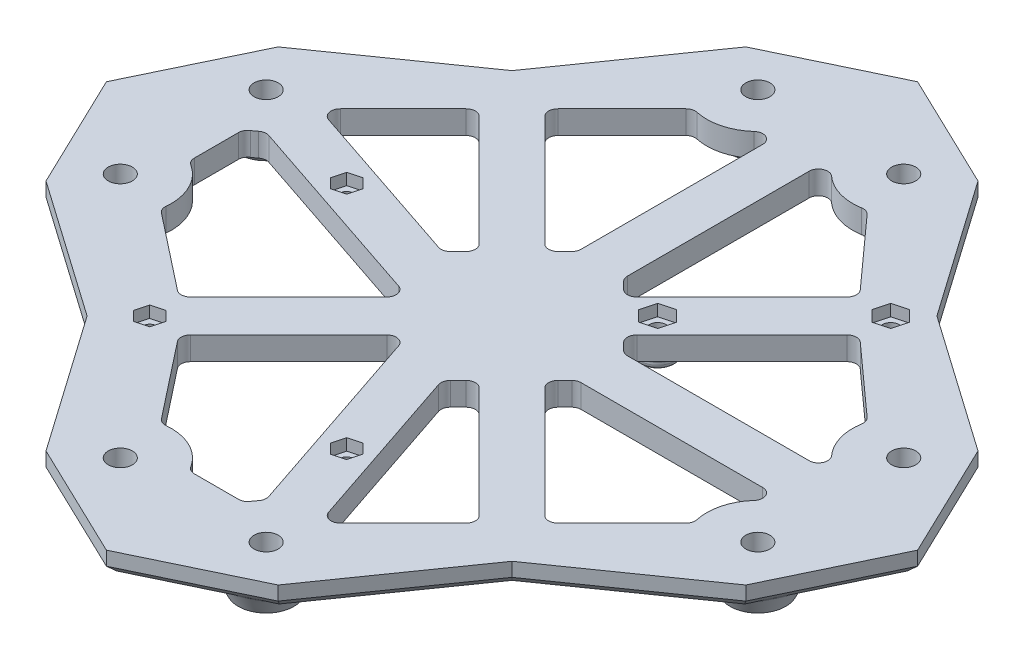
SolidWorks part; units mm, degrees
ref_plane "Front Plane" through (0, 0, 0) normal (0, 0, 1) x (1, 0, 0)
ref_plane "Top Plane" through (0, 0, 0) normal (0, 1, 0) x (1, 0, 0)
ref_plane "Right Plane" through (0, 0, 0) normal (1, 0, 0) x (0, 0, -1)
sketch "Sketch1" plane through (0, 0, 0) normal (0, 1, 0) x (1, 0, 0)
  line L0 (-15.705, 68.65) -> (15.705, 68.65) construction
  line L1 (0, 68.65) -> (0, 0) construction
  line L10 (-15.705, 68.65) -> (0, 87.35) construction
  line L11 (-25.0004, 75.3528) -> (0, 87.35)
  line L12 (0, 87.35) -> (25.0004, 75.3528)
  line L25 (-75.3528, -25.0004) -> (-45.7527, -45.7527)
  line L26 (-25.0004, 75.3528) -> (-15.705, 68.65) construction
  line L27 (0, 87.35) -> (15.705, 68.65) construction
  line L28 (-15.705, 68.65) -> (15.705, 68.65) construction
  line L30 (15.705, 68.65) -> (25.0004, 75.3528) construction
  line L31 (75.3528, 25.0004) -> (87.35, 0)
  line L32 (87.35, 0) -> (75.3528, -25.0004)
  line L33 (68.65, 15.705) -> (68.65, -15.705) construction
  line L34 (68.65, 15.705) -> (87.35, 0) construction
  line L35 (-45.7527, -45.7527) -> (-25.0004, -75.3528)
  line L36 (75.3528, 25.0004) -> (68.65, 15.705) construction
  line L37 (87.35, 0) -> (68.65, -15.705) construction
  line L38 (68.65, 15.705) -> (68.65, -15.705) construction
  line L39 (68.65, -15.705) -> (75.3528, -25.0004) construction
  line L40 (25.0004, -75.3528) -> (0, -87.35)
  line L41 (0, -87.35) -> (-25.0004, -75.3528)
  line L42 (15.705, -68.65) -> (-15.705, -68.65) construction
  line L43 (15.705, -68.65) -> (0, -87.35) construction
  line L44 (25.0004, -75.3528) -> (45.7527, -45.7527)
  line L45 (25.0004, -75.3528) -> (15.705, -68.65) construction
  line L46 (0, -87.35) -> (-15.705, -68.65) construction
  line L47 (15.705, -68.65) -> (-15.705, -68.65) construction
  line L48 (-15.705, -68.65) -> (-25.0004, -75.3528) construction
  line L49 (-75.3528, -25.0004) -> (-87.35, 0)
  line L50 (-87.35, 0) -> (-75.3528, 25.0004)
  line L51 (-68.65, -15.705) -> (-68.65, 15.705) construction
  line L52 (-68.65, -15.705) -> (-87.35, 0) construction
  line L53 (45.7527, -45.7527) -> (75.3528, -25.0004)
  line L54 (-75.3528, -25.0004) -> (-68.65, -15.705) construction
  line L55 (-87.35, 0) -> (-68.65, 15.705) construction
  line L56 (-68.65, -15.705) -> (-68.65, 15.705) construction
  line L57 (-68.65, 15.705) -> (-75.3528, 25.0004) construction
  line L58 (-75.3528, 25.0004) -> (-45.7527, 45.7527)
  line L59 (-45.7527, 45.7527) -> (-25.0004, 75.3528)
  line L60 (25.0004, 75.3528) -> (45.7527, 45.7527)
  line L61 (45.7527, 45.7527) -> (75.3528, 25.0004)
  circle A0 centre (-15.705, 68.65) radius 2.6
  circle A1 centre (15.705, 68.65) radius 2.6
  circle A2 centre (68.65, 15.705) radius 2.6
  circle A3 centre (68.65, -15.705) radius 2.6
  circle A4 centre (15.705, -68.65) radius 2.6
  circle A5 centre (-15.705, -68.65) radius 2.6
  circle A6 centre (-68.65, -15.705) radius 2.6
  circle A7 centre (-68.65, 15.705) radius 2.6
  point P4 (0, 68.65)
  point P42 (0, 0)
  dimension "D1" = 5.2
  dimension "D2" = 31.41
  dimension "D3" = 68.65
  dimension "D5" = 24.42
  dimension "D7" = 11.46
  dimension "D8" = 36.15
  dimension "D9" = 4
  dimension "D4" = 27.73
extrude "Boss-Extrude1" add sketch "Sketch1" along normal blind 5
ref_axis "Axis1" through (-15.705, 5, -68.65) along (0, -1, 0)
ref_plane "Plane1" through (14.012, 0, -6.7241) normal (0.9016, 0, -0.4326) x (0, -1, 0)
sketch "Sketch4" plane through (14.012, 0, -6.7241) normal (0.9016, 0, -0.4326) x (0, -1, 0)
  line L0 (0, 73.1871) -> (4, 73.1871)
  line L1 (4, 73.1871) -> (4, 74.6871)
  line L2 (4, 74.6871) -> (0, 76.6871)
  line L3 (0, 76.6871) -> (0, 73.1871)
  line L4 (-5, 68.6871) -> (0, 68.6871) construction
  point P0 (0, 68.6871)
  dimension "D1" = 4
  dimension "D2" = 8
  dimension "D3" = 4.5
  dimension "D4" = 6
revolve "Revolve1" add sketch "Sketch4" angle 360 about axis through (-15.705, 5, -68.65) along (0, -1, 0)
ref_plane "Plane2" through (0, 0, 0) normal (1, 0, 0) x (0, 0, -1)
mirror "Mirror1" about plane through (0, 0, 0) normal (1, 0, 0) of "Revolve1"
ref_axis "Axis3" through (0, 0, 0) along (0, -1, 0)
pattern_circular "CirPattern1" count 4 every 90 about axis through (0, 0, 0) along (0, -1, 0) of "Revolve1", "Mirror1"
chamfer "Chamfer1" distance 2 angle 45 16 edges at (-60.5527, 0, -35.3765) (-35.3765, 0, -60.5527) (-12.5002, 0, -81.3514) (12.5002, 0, -81.3514) (35.3765, 0, -60.5527) (60.5527, 0, -35.3765) (81.3514, 0, -12.5002) (81.3514, 0, 12.5002) (-81.3514, 0, -12.5002) (-81.3514, 0, 12.5002) (-60.5527, 0, 35.3765) (-35.3765, 0, 60.5527) (-12.5002, 0, 81.3514) (12.5002, 0, 81.3514) (35.3765, 0, 60.5527) (60.5527, 0, 35.3765)
sketch "Sketch5" plane through (0, 0, 0) normal (0, -1, 0) x (1, 0, 0)
  line L0 (-15.705, 68.65) -> (-68.65, 15.705) construction
  line L1 (6.9484, 42.5491) -> (-42.5491, -6.9484) construction
  line L2 (-44.3168, 44.3168) -> (0, 0) construction
  circle A0 centre (-39.0135, 39.0135) radius 1.375
  circle A1 centre (-42.5491, -6.9484) radius 1.375
  circle A3 centre (6.9484, 42.5491) radius 1.375
  point P14 (-17.8003, 17.8003)
  dimension "D1" = 2.75
  dimension "D2" = 70
  dimension "D3" = 30
  dimension "D4" = 7.5
extrude "Cut-Extrude1" cut sketch "Sketch5" against normal blind 10
sketch "Sketch6" plane through (0, 5, 0) normal (0, 1, 0) x (1, 0, 0)
  line L0 (-45.7527, 45.7527) -> (45.7527, -45.7527) construction
  line L1 (-41.8019, 9.7368) -> (-44.5903, 8.9897)
  line L2 (-44.5903, 8.9897) -> (-45.3374, 6.2013)
  line L3 (-45.3374, 6.2013) -> (-43.2962, 4.16)
  line L4 (-43.2962, 4.16) -> (-40.5078, 4.9072)
  line L5 (-40.5078, 4.9072) -> (-39.7607, 7.6956)
  line L6 (-39.7607, 7.6956) -> (-41.8019, 9.7368)
  line L7 (-38.2664, -36.2251) -> (-41.0548, -36.9723)
  line L8 (-41.0548, -36.9723) -> (-41.8019, -39.7607)
  line L9 (-41.8019, -39.7607) -> (-39.7607, -41.8019)
  line L10 (-39.7607, -41.8019) -> (-36.9723, -41.0548)
  line L11 (-36.9723, -41.0548) -> (-36.2251, -38.2664)
  line L12 (-36.2251, -38.2664) -> (-38.2664, -36.2251)
  line L13 (7.6956, -39.7607) -> (4.9072, -40.5078)
  line L14 (4.9072, -40.5078) -> (4.16, -43.2962)
  line L15 (4.16, -43.2962) -> (6.2013, -45.3374)
  line L16 (6.2013, -45.3374) -> (8.9897, -44.5903)
  line L17 (8.9897, -44.5903) -> (9.7368, -41.8019)
  line L18 (9.7368, -41.8019) -> (7.6956, -39.7607)
  circle A3 centre (-42.5491, 6.9484) radius 2.5 construction
  circle A4 centre (-39.0135, -39.0135) radius 2.5 construction
  circle A5 centre (6.9484, -42.5491) radius 2.5 construction
  dimension "D1" = 5
extrude "Cut-Extrude2" cut sketch "Sketch6" against normal blind 2.5
sketch "Sketch7" plane through (0, 0, 0) normal (0, -1, 0) x (1, 0, 0)
  line L0 (0, 0) -> (44.3168, -44.3168) construction
  circle A0 centre (40.7813, -40.7813) radius 1.8
  circle A1 centre (15.679, -15.679) radius 1.8
  dimension "D1" = 3.6
  dimension "D2" = 35.5
  dimension "D3" = 5
extrude "Cut-Extrude3" cut sketch "Sketch7" against normal blind 10
sketch "Sketch8" plane through (0, 5, 0) normal (0, 1, 0) x (1, 0, 0)
  line L0 (-45.7527, 45.7527) -> (45.7527, -45.7527) construction
  line L1 (16.5382, 18.8856) -> (13.3316, 18.0264)
  line L2 (13.3316, 18.0264) -> (12.4723, 14.8198)
  line L3 (12.4723, 14.8198) -> (14.8198, 12.4723)
  line L4 (14.8198, 12.4723) -> (18.0264, 13.3316)
  line L5 (18.0264, 13.3316) -> (18.8856, 16.5382)
  line L6 (18.8856, 16.5382) -> (16.5382, 18.8856)
  line L7 (41.6405, 43.9879) -> (38.4339, 43.1287)
  line L8 (38.4339, 43.1287) -> (37.5746, 39.9221)
  line L9 (37.5746, 39.9221) -> (39.9221, 37.5746)
  line L10 (39.9221, 37.5746) -> (43.1287, 38.4339)
  line L11 (43.1287, 38.4339) -> (43.9879, 41.6405)
  line L12 (43.9879, 41.6405) -> (41.6405, 43.9879)
  circle A0 centre (15.679, 15.679) radius 2.875 construction
  circle A1 centre (40.7813, 40.7813) radius 2.875 construction
  point P10 (41.5254, 38.0042)
  dimension "D1" = 5.75
extrude "Cut-Extrude4" cut sketch "Sketch8" against normal blind 2.5
sketch "Sketch9" plane through (0, 0, 0) normal (0, -1, 0) x (1, 0, 0)
  circle A0 centre (15.679, -15.679) radius 3.8
  circle A1 centre (15.679, -15.679) radius 1.8
  circle A2 centre (40.7813, -40.7813) radius 3.8
  circle A3 centre (40.7813, -40.7813) radius 1.8
  dimension "D1" = 3.6
  dimension "D2" = 7.6
extrude "Boss-Extrude2" add sketch "Sketch9" along normal blind 2.5
fillet "Fillet1" radius 1 5 edges at (15.679, -2.5, -17.479) (15.679, -2.5, -19.479) (40.7813, -2.5, -44.5813) (40.7813, 0, -44.5813) (15.679, 0, -19.479)
fillet "Fillet2" radius 1 8 edges at (-15.705, 0, -60.65) (-60.65, 0, -15.705) (-60.65, 0, 15.705) (-15.705, 0, 60.65) (15.705, 0, 60.65) (60.65, 0, 15.705) (60.65, 0, -15.705) (15.705, 0, -60.65)
sketch "Sketch10" plane through (0, 0, 0) normal (0, -1, 0) x (1, 0, 0)
  line L0 (-12.7279, 0) -> (0, 12.7279)
  line L1 (0, 12.7279) -> (12.7279, 0)
  line L2 (12.7279, 0) -> (0, -12.7279)
  line L3 (0, -12.7279) -> (-12.7279, 0)
  line L4 (-12.7279, 0) -> (12.7279, 0) construction
  line L5 (44.3168, 44.3168) -> (-44.3168, -44.3168) construction
  point P4 (0, 0)
  dimension "D1" = 18
extrude "Cut-Extrude5" cut sketch "Sketch10" against normal blind 2.5
sketch "Sketch11" plane through (0, 0, 0) normal (0, -1, 0) x (1, 0, 0)
  line L0 (0, 12.7279) -> (-12.7279, 0)
  line L1 (-12.7279, 0) -> (0, -12.7279)
  line L2 (0, -12.7279) -> (12.7279, 0)
  line L3 (12.7279, 0) -> (0, 12.7279)
  line L4 (18.3848, 0) -> (0, 18.3848)
  line L5 (0, 18.3848) -> (-18.3848, 0)
  line L6 (-18.3848, 0) -> (0, -18.3848)
  line L7 (0, -18.3848) -> (18.3848, 0)
  dimension "D1" = 4
extrude "Boss-Extrude3" add sketch "Sketch11" along normal blind 4
chamfer "Chamfer3" distance 2.5 angle 45 4 edges at (-9.1924, -4, 9.1924) (-9.1924, -4, -9.1924) (9.1924, -4, 9.1924) (9.1924, -4, -9.1924)
fillet "Fillet4" radius 1 4 edges at (9.1924, 0, 9.1924) (-9.1924, 0, 9.1924) (9.1924, 0, -9.1924) (-9.1924, 0, -9.1924)
sketch "Sketch12" plane through (0, 0, 0) normal (0, -1, 0) x (1, 0, 0)
  line L0 (-44.3168, -44.3168) -> (44.3168, 44.3168) construction
  line L1 (-44.3168, 44.3168) -> (44.3168, -44.3168) construction
  line L2 (-39.0135, 39.0135) -> (-68.65, 15.705) construction
  line L3 (-68.65, 15.705) -> (-42.5491, -6.9484) construction
  line L4 (-42.5491, -6.9484) -> (-19.799, 0) construction
  line L6 (-56.9486, 18.5468) -> (-40.8063, 31.2424)
  line L8 (-38.1557, 31.0846) -> (-17.0129, 9.9419)
  line L16 (-24.0416, 0) -> (0, -24.0416)
  line L17 (0, -24.0416) -> (24.0416, 0)
  line L18 (24.0416, 0) -> (0, 24.0416)
  line L19 (0, 24.0416) -> (-24.0416, 0)
  line L20 (-24.0416, 0) -> (0, -24.0416) construction
  line L21 (0, -24.0416) -> (24.0416, 0) construction
  line L22 (24.0416, 0) -> (0, 24.0416) construction
  line L23 (0, 24.0416) -> (-24.0416, 0) construction
  line L24 (40.7813, -40.7813) -> (15.705, -68.65) construction
  line L25 (15.705, -68.65) -> (-15.705, -68.65) construction
  line L26 (-68.65, -15.705) -> (-15.705, -68.65) construction
  line L27 (-7.0711, -16.9706) -> (-5.5858, -18.4558)
  line L28 (9.8995, -16.9706) -> (32.5502, -39.6213)
  line L29 (32.6227, -42.3732) -> (19.3154, -57.1624)
  line L31 (-19.9154, -57.3685) -> (-33.6922, -43.5917)
  line L32 (-33.6922, -40.7633) -> (-9.8995, -16.9706)
  line L45 (-42.5491, -6.9484) -> (-68.65, -15.705) construction
  line L47 (-56.3449, -16.8506) -> (-20.7134, -4.8967)
  line L48 (-57.1229, -20.161) -> (-43.5917, -33.6922)
  line L49 (-40.7633, -33.6922) -> (-16.9706, -9.8995)
  line L51 (-68.65, 15.705) -> (-68.65, -15.705) construction
  line L52 (-63.65, 4.7505) -> (-63.65, -4.7505)
  line L53 (0, -19.799) -> (0, -68.65) construction
  line L54 (-59.8548, -7.4804) -> (-17.791, 6.6315)
  line L55 (-5, -19.8701) -> (-5, -58.9948)
  line L57 (5, -19.8701) -> (5, -58.9948)
  line L62 (-18.663, -5.3786) -> (-16.9706, -7.0711)
  line L64 (5.5858, -18.4558) -> (7.0711, -16.9706)
  line L66 (42.3732, -32.6227) -> (57.1624, -19.3154)
  line L67 (16.9706, -9.8995) -> (39.6213, -32.5502)
  line L68 (18.4558, -5.5858) -> (16.9706, -7.0711)
  line L69 (19.8701, -5) -> (58.9948, -5)
  line L70 (19.8701, 5) -> (58.9948, 5)
  line L71 (16.9706, 7.0711) -> (18.4558, 5.5858)
  line L72 (40.7633, 33.6922) -> (16.9706, 9.8995)
  line L73 (57.3685, 19.9154) -> (43.5917, 33.6922)
  line L74 (16.8506, 56.3449) -> (4.8967, 20.7134)
  line L75 (5.3786, 18.663) -> (7.0711, 16.9706)
  line L76 (33.6922, 40.7633) -> (9.8995, 16.9706)
  line L77 (20.161, 57.1229) -> (33.6922, 43.5917)
  line L78 (-4.7505, 63.65) -> (4.7505, 63.65)
  line L79 (-18.5468, 56.9486) -> (-31.2424, 40.8063)
  line L80 (-31.0846, 38.1557) -> (-9.9419, 17.0129)
  line L81 (7.4804, 59.8548) -> (-6.6315, 17.791)
  circle A0 centre (-39.0135, 39.0135) radius 5 construction
  circle A2 centre (-42.5491, -6.9484) radius 5 construction
  circle A3 centre (-68.65, 15.705) radius 11 construction
  circle A4 centre (-68.65, -15.705) radius 11 construction
  circle A9 centre (-15.705, -68.65) radius 11 construction
  circle A10 centre (15.705, -68.65) radius 11 construction
  arc A34 (-8.3392, -60.4802) -> (-18.071, -57.9075) centre (-15.705, -68.65) ccw
  arc A105 (-62.7269, 6.4358) -> (-57.7026, 16.7794) centre (-68.65, 15.705) ccw
  arc A106 (-61.7461, -7.1413) -> (-62.7269, -6.4358) centre (-68.65, -15.705) ccw
  arc A108 (-16.9706, -9.8995) -> (-16.9706, -7.0711) centre (-18.3848, -8.4853) ccw
  arc A109 (-20.7134, -4.8967) -> (-18.663, -5.3786) centre (-20.0772, -6.7928) cw
  arc A110 (-40.7633, -33.6922) -> (-43.5917, -33.6922) centre (-42.1775, -32.278) cw
  arc A111 (-57.1229, -20.161) -> (-56.3449, -16.8506) centre (-55.7087, -18.7468) cw
  arc A112 (-59.8548, -7.4804) -> (-61.7461, -7.1413) centre (-60.4909, -5.5843) cw
  arc A113 (-62.7269, -6.4358) -> (-63.65, -4.7505) centre (-61.65, -4.7505) cw
  arc A114 (-63.65, 4.7505) -> (-62.7269, 6.4358) centre (-61.65, 4.7505) cw
  arc A115 (-57.7026, 16.7794) -> (-56.9486, 18.5468) centre (-55.7122, 16.9748) cw
  arc A116 (-40.8063, 31.2424) -> (-38.1557, 31.0846) centre (-39.5699, 29.6704) cw
  arc A117 (-17.791, 6.6315) -> (-17.0129, 9.9419) centre (-18.4271, 8.5276) ccw
  arc A118 (17.5019, -57.7978) -> (8.3392, -60.4802) centre (15.705, -68.65) ccw
  arc A119 (8.3392, -60.4802) -> (5, -58.9948) centre (7, -58.9948) cw
  arc A120 (-5, -58.9948) -> (-8.3392, -60.4802) centre (-7, -58.9948) cw
  arc A121 (19.3154, -57.1624) -> (17.5019, -57.7978) centre (17.8287, -55.8246) cw
  arc A122 (32.5502, -39.6213) -> (32.6227, -42.3732) centre (31.136, -41.0355) cw
  arc A123 (-18.071, -57.9075) -> (-19.9154, -57.3685) centre (-18.5012, -55.9543) cw
  arc A124 (-33.6922, -43.5917) -> (-33.6922, -40.7633) centre (-32.278, -42.1775) cw
  arc A125 (9.8995, -16.9706) -> (7.0711, -16.9706) centre (8.4853, -18.3848) ccw
  arc A126 (5, -19.8701) -> (5.5858, -18.4558) centre (7, -19.8701) cw
  arc A127 (-5, -19.8701) -> (-5.5858, -18.4558) centre (-7, -19.8701) ccw
  arc A128 (-7.0711, -16.9706) -> (-9.8995, -16.9706) centre (-8.4853, -18.3848) ccw
  arc A129 (57.7978, -17.5019) -> (60.4802, -8.3392) centre (68.65, -15.705) cw
  arc A130 (57.1624, -19.3154) -> (57.7978, -17.5019) centre (55.8246, -17.8287) ccw
  arc A131 (39.6213, -32.5502) -> (42.3732, -32.6227) centre (41.0355, -31.136) ccw
  arc A132 (16.9706, -9.8995) -> (16.9706, -7.0711) centre (18.3848, -8.4853) cw
  arc A133 (19.8701, -5) -> (18.4558, -5.5858) centre (19.8701, -7) ccw
  arc A134 (60.4802, -8.3392) -> (58.9948, -5) centre (58.9948, -7) ccw
  arc A135 (60.4802, 8.3392) -> (57.9075, 18.071) centre (68.65, 15.705) cw
  arc A136 (58.9948, 5) -> (60.4802, 8.3392) centre (58.9948, 7) ccw
  arc A137 (19.8701, 5) -> (18.4558, 5.5858) centre (19.8701, 7) cw
  arc A138 (16.9706, 7.0711) -> (16.9706, 9.8995) centre (18.3848, 8.4853) cw
  arc A139 (57.9075, 18.071) -> (57.3685, 19.9154) centre (55.9543, 18.5012) ccw
  arc A140 (43.5917, 33.6922) -> (40.7633, 33.6922) centre (42.1775, 32.278) ccw
  arc A141 (4.8967, 20.7134) -> (5.3786, 18.663) centre (6.7928, 20.0772) ccw
  arc A142 (9.8995, 16.9706) -> (7.0711, 16.9706) centre (8.4853, 18.3848) cw
  arc A143 (33.6922, 40.7633) -> (33.6922, 43.5917) centre (32.278, 42.1775) ccw
  arc A144 (20.161, 57.1229) -> (16.8506, 56.3449) centre (18.7468, 55.7087) ccw
  arc A145 (7.1413, 61.7461) -> (6.4358, 62.7269) centre (15.705, 68.65) cw
  arc A146 (6.4358, 62.7269) -> (4.7505, 63.65) centre (4.7505, 61.65) ccw
  arc A147 (-4.7505, 63.65) -> (-6.4358, 62.7269) centre (-4.7505, 61.65) ccw
  arc A148 (-6.4358, 62.7269) -> (-16.7794, 57.7026) centre (-15.705, 68.65) cw
  arc A149 (-16.7794, 57.7026) -> (-18.5468, 56.9486) centre (-16.9748, 55.7122) ccw
  arc A150 (-31.2424, 40.8063) -> (-31.0846, 38.1557) centre (-29.6704, 39.5699) ccw
  arc A151 (7.4804, 59.8548) -> (7.1413, 61.7461) centre (5.5843, 60.4909) ccw
  arc A152 (-6.6315, 17.791) -> (-9.9419, 17.0129) centre (-8.5276, 18.4271) cw
  point P28 (-15.5563, -8.4853)
  point P42 (-19.539, -4.5027)
  point P53 (-5, -66.1196)
  point P61 (-60.9512, -7.8483)
  point P65 (-63.65, -5.907)
  point P68 (-63.65, 5.907)
  point P71 (-57.8576, 17.8319)
  point P77 (18.5418, -58.0221)
  point P84 (-19.0977, -58.1863)
  point P86 (21.2248, -28.2959)
  point P91 (8.4853, -15.5563)
  point P95 (5, -19.0416)
  point P99 (-5, -19.0416)
  point P104 (-8.4853, -15.5563)
  dimension "D1" = 10
  dimension "D3" = 22
  dimension "D8" = 5
  dimension "D14" = 2
  dimension "D19" = 2
  dimension "D6" = 2
  dimension "D17" = 2
  dimension "D12" = 2
  dimension "D2" = 3
  dimension "D4" = 5
  dimension "D5" = 5
  dimension "D7" = 5
  dimension "D9" = 5
  dimension "D10" = 5
  dimension "D11" = 5
  dimension "D13" = 5
  dimension "D15" = 5
  dimension "D16" = 5
  dimension "D18" = 5
  dimension "D23" = 5
  dimension "D24" = 5
extrude "Cut-Extrude6" cut sketch "Sketch12" against normal through all
